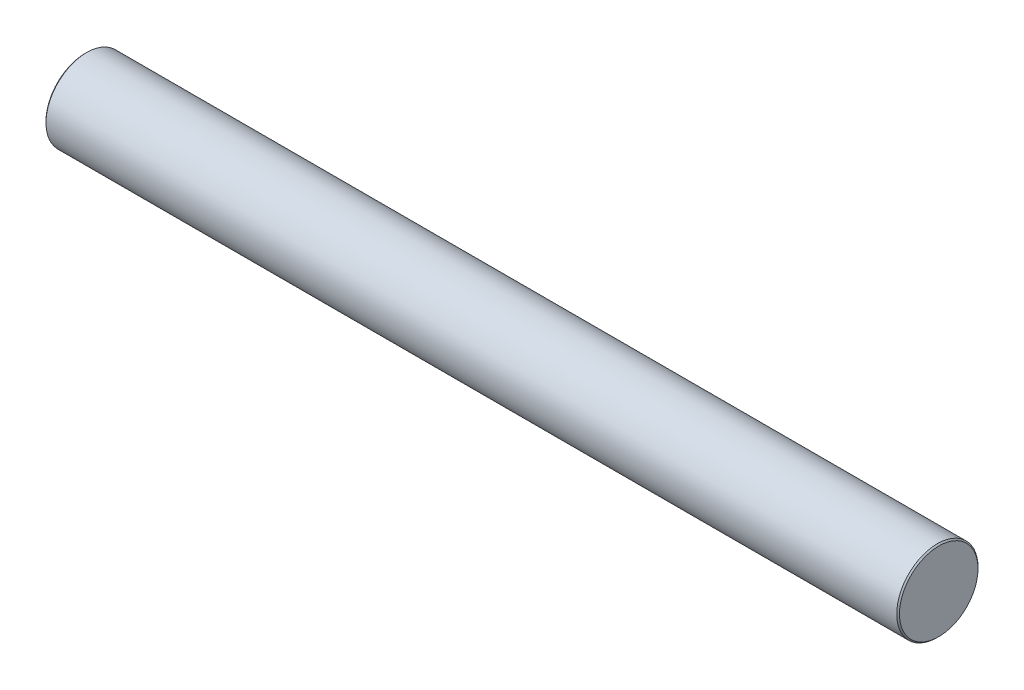
SolidWorks part; units mm, degrees
ref_plane "Front Plane" through (0, 0, 0) normal (0, 0, 1) x (1, 0, 0)
ref_plane "Top Plane" through (0, 0, 0) normal (0, 1, 0) x (1, 0, 0)
ref_plane "Right Plane" through (0, 0, 0) normal (1, 0, 0) x (0, 0, -1)
sketch "Sketch1" plane through (0, 0, 0) normal (0, 0, 1) x (1, 0, 0)
  line L0 (-31.5, 0) -> (31.5, 0)
  line L2 (-31.5, 0) -> (-31.5, 3)
  line L3 (-31.5, 3) -> (31.5, 3)
  line L4 (31.5, -3) -> (31.5, 3)
  line L5 (0, 3) -> (0, 0) construction
  line L6 (-31.5, 0) -> (31.5, 0) construction
  line L7 (-18.8524, 0) -> (-46.8976, 0) construction
  point P0 (0, 0)
  dimension "D1" = 3
  dimension "D2" = 63
revolve "Revolve1" add sketch "Sketch1" angle 360 about L7 region at (0, 1.5, 0)
chamfer "Chamfer1" distance 0.1 angle 45 2 edges at (-31.5, 3, 0) (31.5, 3, 0)
